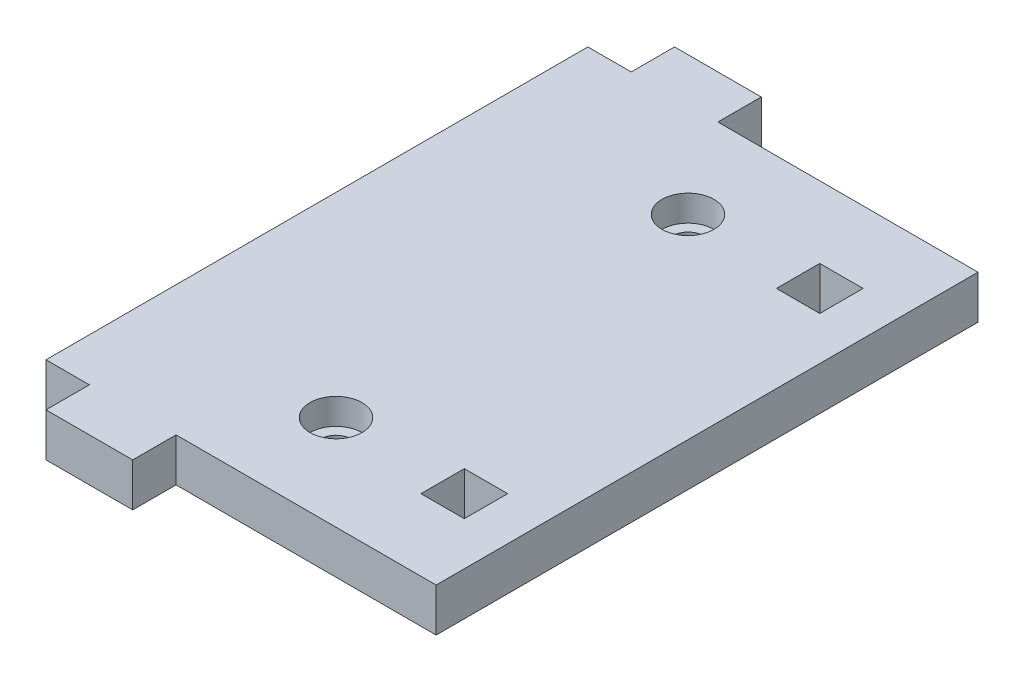
SolidWorks part; units mm, degrees
ref_plane "Front Plane" through (0, 0, 0) normal (0, 0, 1) x (1, 0, 0)
ref_plane "Top Plane" through (0, 0, 0) normal (0, 1, 0) x (1, 0, 0)
ref_plane "Right Plane" through (0, 0, 0) normal (1, 0, 0) x (0, 0, -1)
sketch "Sketch1" plane through (0, 0, 0) normal (0, 1, 0) x (1, 0, 0)
  line L0 (-116.895, -11.7675) -> (73.0758, -11.7675) construction
  line L1 (-21.9096, 19.4825) -> (23.0904, 19.4825)
  line L2 (-21.9096, 19.4825) -> (-21.9096, -43.0175)
  line L3 (-21.9096, -43.0175) -> (23.0904, -43.0175)
  line L4 (23.0904, 19.4825) -> (23.0904, -43.0175)
  line L5 (-16.9096, 19.4825) -> (-6.9096, 19.4825)
  line L6 (-16.9096, 19.4825) -> (-16.9096, 24.4825)
  line L7 (-16.9096, 24.4825) -> (-6.9096, 24.4825)
  line L8 (-6.9096, 19.4825) -> (-6.9096, 24.4825)
  line L9 (13.0904, -29.7675) -> (18.0904, -29.7675)
  line L10 (13.0904, 11.2325) -> (18.0904, 11.2325)
  line L11 (13.0904, 11.2325) -> (13.0904, 6.2325)
  line L12 (13.0904, 6.2325) -> (18.0904, 6.2325)
  line L13 (18.0904, 11.2325) -> (18.0904, 6.2325)
  line L14 (18.0904, -34.7675) -> (18.0904, -29.7675)
  line L15 (13.0904, -34.7675) -> (18.0904, -34.7675)
  line L16 (13.0904, -34.7675) -> (13.0904, -29.7675)
  line L17 (-16.9096, -48.0175) -> (-6.9096, -48.0175)
  line L18 (-6.9096, -43.0175) -> (-6.9096, -48.0175)
  line L19 (-16.9096, -43.0175) -> (-6.9096, -43.0175)
  line L20 (-16.9096, -43.0175) -> (-16.9096, -48.0175)
  circle A0 centre (0.5904, 8.5325) radius 1.75
  circle A1 centre (0.5904, -32.0675) radius 1.75
  point P11 (-21.9096, -11.7675)
  dimension "D10" = 22.5
  dimension "D1" = 45
  dimension "D2" = 62.5
  dimension "D3" = 10
  dimension "D4" = 5
  dimension "D5" = 5
  dimension "D6" = 18
  dimension "D7" = 5
  dimension "D8" = 5
  dimension "D9" = 5
  dimension "D11" = 20.3
extrude "Boss-Extrude1" add sketch "Sketch1" along normal blind 5 contours L2 L0 L4 L1 A0 L10 L13 L12 L11 | L0 L2 L3 L4 L15 L16 L9 L14 A1 | L3 L20 L17 L18 | L1 L8 L7 L6 region at (0.317, 0, -3.7359) region at (0.317, 0, 27.2708) region at (-11.9096, 0, -21.9825) region at (-11.9096, 0, 45.5175)
sketch "Sketch2" plane through (0, 5, 0) normal (0, 1, 0) x (1, 0, 0)
  circle A0 centre (0.5904, -32.0675) radius 3
  circle A1 centre (0.5904, 8.5325) radius 3
extrude "Cut-Extrude1" cut sketch "Sketch2" against normal blind 3
